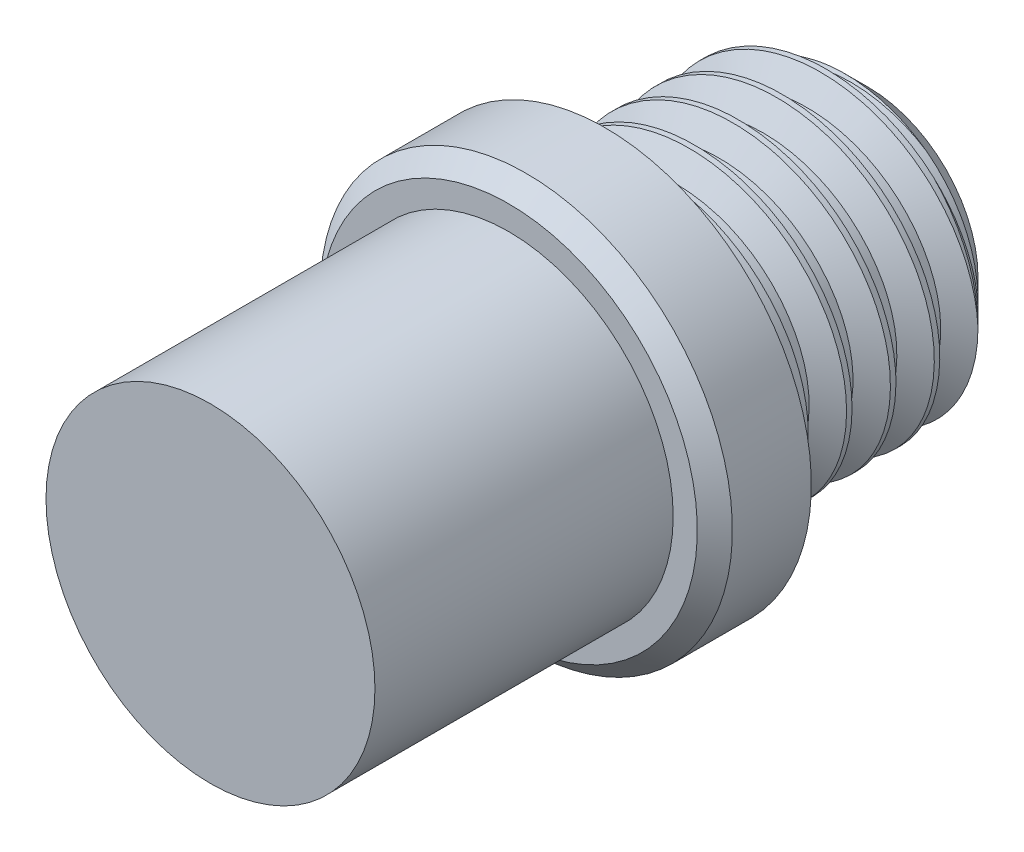
SolidWorks part; units mm, degrees
ref_plane "Front Plane" through (0, 0, 0) normal (0, 0, 1) x (1, 0, 0)
ref_plane "Top Plane" through (0, 0, 0) normal (0, 1, 0) x (1, 0, 0)
ref_plane "Right Plane" through (0, 0, 0) normal (1, 0, 0) x (0, 0, -1)
sketch "Sketch2" plane through (0, 0, 0) normal (0, 1, 0) x (1, 0, 0)
  line L0 (0, 0) -> (3.75, 0)
  line L1 (3.75, 0) -> (3.75, 6.8)
  line L2 (3.75, 6.8) -> (4.3, 6.8)
  line L3 (4.7, 7.2) -> (4.7, 9)
  line L4 (4.7, 9) -> (3.5, 9)
  line L5 (3.5, 9) -> (3.5, 15)
  line L6 (3.5, 15) -> (2.25, 15)
  line L10 (2.25, 15) -> (2.25, 6)
  line L11 (2.25, 6) -> (0, 6)
  line L12 (0, 6) -> (0, 0)
  line L13 (4.3, 6.8) -> (4.7, 7.2)
  dimension "D1" = 3.75
  dimension "D2" = 2.2
  dimension "D3" = 2.25
  dimension "D4" = 15
  dimension "D5" = 3.5
  dimension "D6" = 9
  dimension "D7" = 4.7
  dimension "D8" = 1.8
  dimension "D9" = 45
  dimension "D10" = 9
revolve "Revolve1" add sketch "Sketch2" angle 360 about L12
chamfer "Chamfer1" distance 1 angle 45 1 edges at (-3.5, 0, -15)
thread "Thread1" pitch 1 start angle 0, offset 1, length 0, pitch 1, diameter 7
ref_plane "Plane1" through (3.5, 0, -15) normal (0, -1, 0) x (1, 0, 0)
sketch "Thread Profile1" plane through (3.5, 0, -15) normal (0, -1, 0) x (1, 0, 0)
  line L0 (0, 0) -> (0, 1) construction
  line L11 (0, 0) -> (0, 0.875)
  line L12 (0, 0.875) -> (-0.5413, 0.5625)
  line L13 (-0.5413, 0.5625) -> (-0.5413, 0.3125)
  line L15 (-0.5413, 0.3125) -> (0, 0)
  line L17 (-0.5413, 0.4375) -> (0, 0.4375) construction
  point P2 (0, 0)
  dimension "Pitch" = 1
  dimension "Profile_Angle" = 60
  dimension "Profile_Land" = 0.25
  dimension "Profile_Height" = 0.5413
